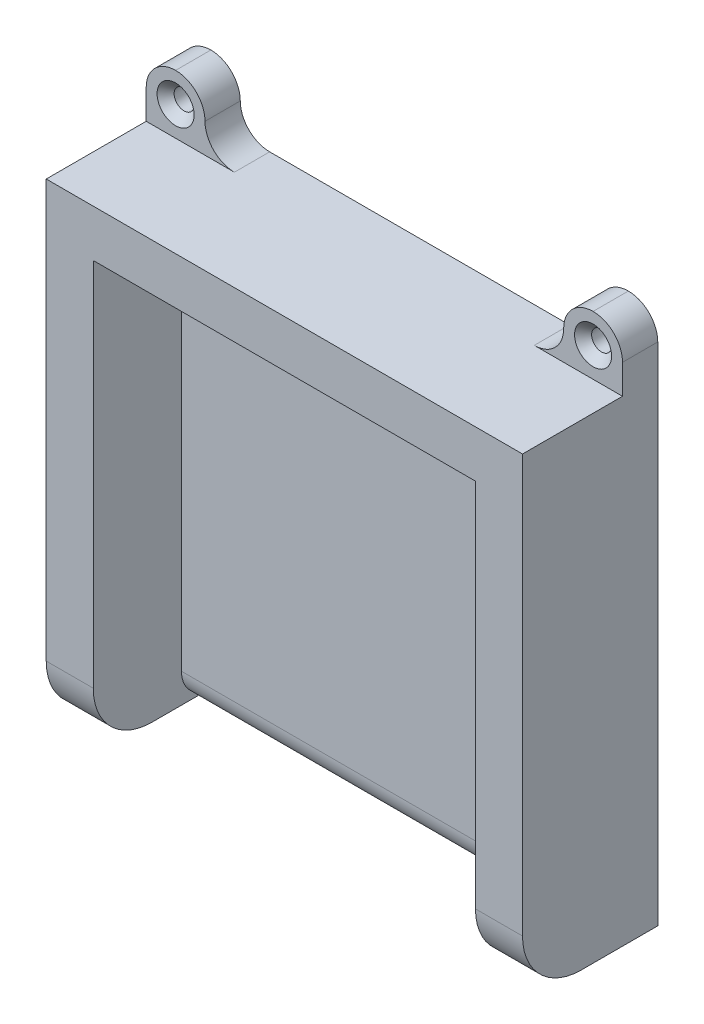
SolidWorks part; units mm, degrees
ref_plane "Plan de face" through (0, 0, 0) normal (0, 0, 1) x (1, 0, 0)
ref_plane "Plan de dessus" through (0, 0, 0) normal (0, 1, 0) x (1, 0, 0)
ref_plane "Plan de droite" through (0, 0, 0) normal (1, 0, 0) x (0, 0, -1)
sketch "Esquisse1" plane through (0, 0, 0) normal (0, 0, 1) x (1, 0, 0)
  line L1 (0, 0) -> (81, 0)
  line L2 (0, 0) -> (0, 81)
  line L3 (0, 81) -> (81, 81)
  line L4 (81, 0) -> (81, 81)
  dimension "D1" = 81
  dimension "D2" = 81
extrude "Boss.-Extru.1" add sketch "Esquisse1" along normal blind 8
sketch "Esquisse2" plane through (0, 0, 8) normal (0, 0, 1) x (1, 0, 0)
  line L1 (0, 81) -> (81, 81)
  line L3 (8, 73) -> (73, 73)
  line L4 (81, 81) -> (0, 81) construction
  line L6 (8, 73) -> (8, 0)
  line L8 (0, 81) -> (0, 0)
  line L9 (0, 0) -> (81, 0)
  line L10 (81, 0) -> (81, 81)
  line L11 (81, 81) -> (0, 81)
  line L12 (0, 81) -> (0, 0)
  line L13 (0, 0) -> (8, 0)
  line L14 (81, 0) -> (81, 81)
  line L16 (73, 73) -> (73, 0)
  line L17 (0, 0) -> (81, 0) construction
  line L19 (73, 0) -> (81, 0)
  dimension "D2" = 8
  dimension "D3" = 8
  dimension "D4" = 8
extrude "Boss.-Extru.2" add sketch "Esquisse2" along normal blind 15
fillet "Congé1" radius 10 2 edges at (77, 0, 23) (4, 0, 23)
fillet "Congé2" radius 5 1 edges at (40.5, 0, 8)
sketch "Esquisse3" plane through (0, 81, 0) normal (0, 1, 0) x (1, 0, 0)
  line L4 (40.5, 0) -> (40.5, -30.4724) construction
  line L5 (0, 0) -> (10, 0)
  line L6 (0, 0) -> (0, -6)
  line L7 (0, -6) -> (10, -6)
  line L8 (81, 0) -> (0, 0)
  line L9 (0, 0) -> (0, -23)
  line L10 (0, -23) -> (81, -23)
  line L11 (81, -23) -> (81, 0)
  line L12 (81, 0) -> (0, 0) construction
  line L13 (0, 0) -> (0, -23) construction
  line L14 (0, -23) -> (81, -23) construction
  line L15 (81, -23) -> (81, 0) construction
  line L16 (10, 0) -> (10, -6)
  line L17 (81, -6) -> (71, -6)
  line L18 (71, 0) -> (71, -6)
  line L19 (81, 0) -> (71, 0)
  line L20 (81, 0) -> (81, -6)
  dimension "D2" = 10
  dimension "D3" = 6
  dimension "D1" = 0
extrude "Boss.-Extru.3" add sketch "Esquisse3" along normal blind 10
fillet "Congé3" radius 5 6 edges at (0, 91, 3) (10, 91, 3) (10, 81, 3) (71, 81, 3) (71, 91, 3) (81, 91, 3)
sketch "Esquisse4" plane through (0, 0, 6) normal (0, 0, 1) x (1, 0, 0)
  line L0 (40.5, 81) -> (40.5, 90.0778) construction
  line L1 (81, 81) -> (0, 81) construction
  circle A0 centre (76, 86) radius 1
  circle A1 centre (5, 86) radius 1
  dimension "D1" = 2
hole_wizard "Fraisage pour vis à tête fraisée M31" positions "Esquisse5" profile "Esquisse6" countersink size "M3" standard "ISO" end condition through all
sketch "Esquisse5" plane through (0, 0, 6) normal (0, 0, 1) x (1, 0, 0)
  point P0 (76, 86)
  point P3 (5, 86)
sketch "Esquisse6" plane through (76, 86, 6) normal (1, 0, 0) x (0, -1, 0)
  line L0 (0, 0) -> (0, 6)
  line L1 (0, 6) -> (1.7, 6)
  line L2 (1.7, 6) -> (1.7, 1.45)
  line L3 (1.7, 1.45) -> (3.15, 0)
  line L5 (3.15, 0) -> (0, 0)
  line L6 (-1.7, 1.45) -> (-3.15, 0) construction
  line L11 (0, -6.35) -> (0, 107.95) construction
  dimension "Diamètre du perçage jusqu'au prochain" = 3.4
  dimension "Profondeur du perçage jusqu'au prochain" = 6
  dimension "Diamètre du fraisage entrant" = 6.3
  dimension "Angle du fraisage entrant" = 90
equation "\"epaiss_cadre\"= 8"
equation "\"D2@Esquisse1\"=\"epaiss_cadre\"*2+65"
equation "\"D1@Esquisse1\"=\"epaiss_cadre\"*2+65"
equation "\"D1@Boss.-Extru.1\"=\"epaiss_cadre\""
equation "\"D2@Esquisse2\"=\"epaiss_cadre\""
equation "\"D3@Esquisse2\"=\"epaiss_cadre\""
equation "\"D4@Esquisse2\"=\"epaiss_cadre\""
